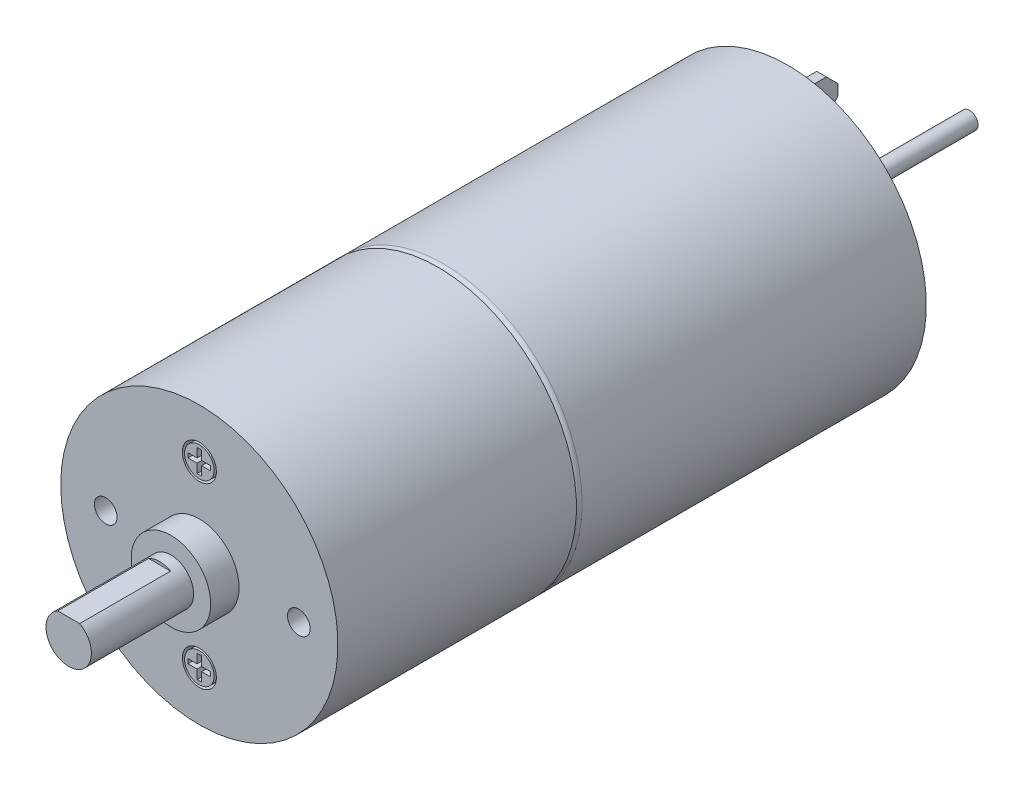
SolidWorks part; units mm, degrees
ref_plane "Ön Düzlem" through (0, 0, 0) normal (0, 0, 1) x (1, 0, 0)
ref_plane "Üst Düzlem" through (0, 0, 0) normal (0, 1, 0) x (1, 0, 0)
ref_plane "Sağ Düzlem" through (0, 0, 0) normal (1, 0, 0) x (0, 0, -1)
sketch "Çizim1" plane through (0, 0, 0) normal (0, 0, 1) x (1, 0, 0)
  circle A0 centre (-41.1435, 10.1614) radius 12.2
  dimension "D1" = 24.4
extrude "Yükseklik-Ekstrüzyon1" add sketch "Çizim1" along normal blind 30.8
fillet "Radyus1" radius 0.5 1 edges at (-28.9435, 10.1614, 30.8)
sketch "Çizim2" plane through (0, 0, 30.8) normal (0, 0, 1) x (1, 0, 0)
  circle A0 centre (-41.1435, 10.1614) radius 12.2
extrude "Yükseklik-Ekstrüzyon2" add sketch "Çizim2" along normal blind 21
sketch "Çizim3" plane through (0, 0, 51.8) normal (0, 0, 1) x (1, 0, 0)
  circle A0 centre (-41.1435, 10.1614) radius 3.5
  dimension "D1" = 7
extrude "Yükseklik-Ekstrüzyon3" add sketch "Çizim3" along normal blind 2.5
sketch "Çizim4" plane through (0, 0, 54.3) normal (0, 0, 1) x (1, 0, 0)
  circle A0 centre (-41.1435, 10.1614) radius 2
  dimension "D1" = 4
extrude "Yükseklik-Ekstrüzyon4" add sketch "Çizim4" along normal blind 9
sketch "Çizim5" plane through (0, 0, 51.8) normal (0, 0, 1) x (1, 0, 0)
  circle A0 centre (-49.3847, 10.1614) radius 1
  circle A1 centre (-32.3847, 10.1614) radius 1
  dimension "D2" = 2
  dimension "D3" = 2
  dimension "D1" = 17
extrude "Kes-Ekstrüzyon1" cut sketch "Çizim5" against normal blind 10
sketch "Çizim6" plane through (0, 0, 51.8) normal (0, 0, 1) x (1, 0, 0)
  line L0 (-40.9435, 17.0114) -> (-40.9435, 17.8114)
  line L1 (-40.9435, 19.0114) -> (-41.3435, 19.0114)
  line L2 (-41.3435, 3.3114) -> (-41.3435, 2.5114)
  line L3 (-41.3435, 1.3114) -> (-40.9435, 1.3114)
  line L4 (-40.9435, 1.3114) -> (-40.9435, 2.1114)
  line L5 (-40.9435, 3.3114) -> (-41.3435, 3.3114)
  line L6 (-41.3435, 2.5114) -> (-42.1435, 2.5114)
  line L7 (-42.1435, 2.5114) -> (-42.1435, 2.1114)
  line L8 (-42.1435, 2.1114) -> (-41.3435, 2.1114)
  line L9 (-40.1435, 2.1114) -> (-40.1435, 2.5114)
  line L10 (-40.1435, 2.5114) -> (-40.9435, 2.5114)
  line L11 (-41.3435, 2.1114) -> (-41.3435, 1.3114)
  line L12 (-40.9435, 2.5114) -> (-40.9435, 3.3114)
  line L13 (-40.9435, 2.1114) -> (-40.1435, 2.1114)
  line L14 (-41.3435, 19.0114) -> (-41.3435, 18.2114)
  line L15 (-41.3435, 17.0114) -> (-40.9435, 17.0114)
  line L16 (-40.9435, 17.8114) -> (-40.1435, 17.8114)
  line L17 (-40.1435, 17.8114) -> (-40.1435, 18.2114)
  line L18 (-40.1435, 18.2114) -> (-40.9435, 18.2114)
  line L19 (-42.1435, 18.2114) -> (-42.1435, 17.8114)
  line L20 (-42.1435, 17.8114) -> (-41.3435, 17.8114)
  line L21 (-40.9435, 18.2114) -> (-40.9435, 19.0114)
  line L22 (-41.3435, 17.8114) -> (-41.3435, 17.0114)
  line L23 (-41.3435, 18.2114) -> (-42.1435, 18.2114)
  circle A2 centre (-41.1435, 2.3114) radius 1.5
  circle A3 centre (-41.1435, 18.0114) radius 1.5
  circle A4 centre (-41.1435, 18.0114) radius 1.3
  circle A5 centre (-41.1435, 2.3114) radius 1.3
  point P34 (-41.1435, 10.1614)
  dimension "D2" = 3
  dimension "D3" = 0.2
  dimension "D4" = 2
  dimension "D5" = 0.8
  dimension "D6" = 0.8
  dimension "D7" = 0.8
  dimension "D8" = 0.8
  dimension "D9" = 0.4
  dimension "D10" = 0.4
  dimension "D11" = 0.2
  dimension "D12" = 0.2
ref_axis "Eksen1" through (-41.1435, 10.1614, 78.5769) along (0, 0, -1)
extrude "Kes-Ekstrüzyon2" cut sketch "Çizim6" against normal blind 1 contours L4 L13 L9 L10 L12 L5 L2 L6 L7 L8 L11 L3 | A2 A5 | L14 L23 L19 L20 L22 L15 L0 L16 L17 L18 L21 L1 | A3 A4 region at (-41.1435, 18.0114, 51.8) region at (-41.1435, 2.3114, 51.8) region at (-42.601, 2.3114, 51.8) region at (-42.601, 18.0114, 51.8)
sketch "Çizim8" plane through (0, 0, 63.3) normal (0, 0, 1) x (1, 0, 0)
  line L0 (-42.1117, 11.9114) -> (-40.1752, 11.9114)
  arc A0 (-40.1752, 11.9114) -> (-42.1117, 11.9114) centre (-41.1435, 10.1614) ccw
  dimension "D2" = 4
  dimension "D1" = 1.75
extrude "Kes-Ekstrüzyon3" cut sketch "Çizim8" against normal blind 8
sketch "Çizim9" plane through (0, 0, 0) normal (0, 0, -1) x (-1, 0, 0)
  circle A0 centre (41.1435, 10.1614) radius 3.25
  dimension "D1" = 6.5
extrude "Yükseklik-Ekstrüzyon5" add sketch "Çizim9" along normal blind 1
sketch "Çizim10" plane through (0, 0, -1) normal (0, 0, -1) x (-1, 0, 0)
  circle A0 centre (41.1435, 10.1614) radius 0.75
  dimension "D1" = 1.5
extrude "Yükseklik-Ekstrüzyon6" add sketch "Çizim10" along normal blind 15
sketch "Çizim11" plane through (0, 0, 0) normal (0, 0, -1) x (-1, 0, 0)
  line L3 (40.733, 20.1614) -> (41.5855, 20.1614)
  line L4 (40.733, 20.1614) -> (40.733, 17.1614)
  line L5 (40.733, 17.1614) -> (41.5855, 17.1614)
  line L6 (41.5855, 20.1614) -> (41.5855, 17.1614)
  line L7 (40.733, 3.1614) -> (41.5855, 3.1614)
  line L8 (40.733, 3.1614) -> (40.733, 0.1614)
  line L9 (40.733, 0.1614) -> (41.5855, 0.1614)
  line L10 (41.5855, 3.1614) -> (41.5855, 0.1614)
  dimension "D3" = 3
  dimension "D4" = 3
extrude "Yükseklik-Ekstrüzyon7" add sketch "Çizim11" along normal blind 4
sketch "Çizim12" plane through (-40.733, 0, 0) normal (1, 0, 0) x (0, 0, -1)
  line L0 (4, 17.1614) -> (0, 17.1614) construction
  line L1 (4, 3.1614) -> (0, 3.1614) construction
  circle A0 centre (1.9254, 18.6614) radius 0.75
  circle A1 centre (1.9254, 1.6614) radius 0.75
  dimension "D1" = 1.5
  dimension "D2" = 1.5
  dimension "D3" = 1.5
  dimension "D4" = 1.5
extrude "Kes-Ekstrüzyon4" cut sketch "Çizim12" against normal blind 4
chamfer "Pah1" distance 1 angle 45 4 edges at (-41.1593, 0.1614, -4) (-41.1593, 3.1614, -4) (-41.1593, 20.1614, -4) (-41.1593, 17.1614, -4)
